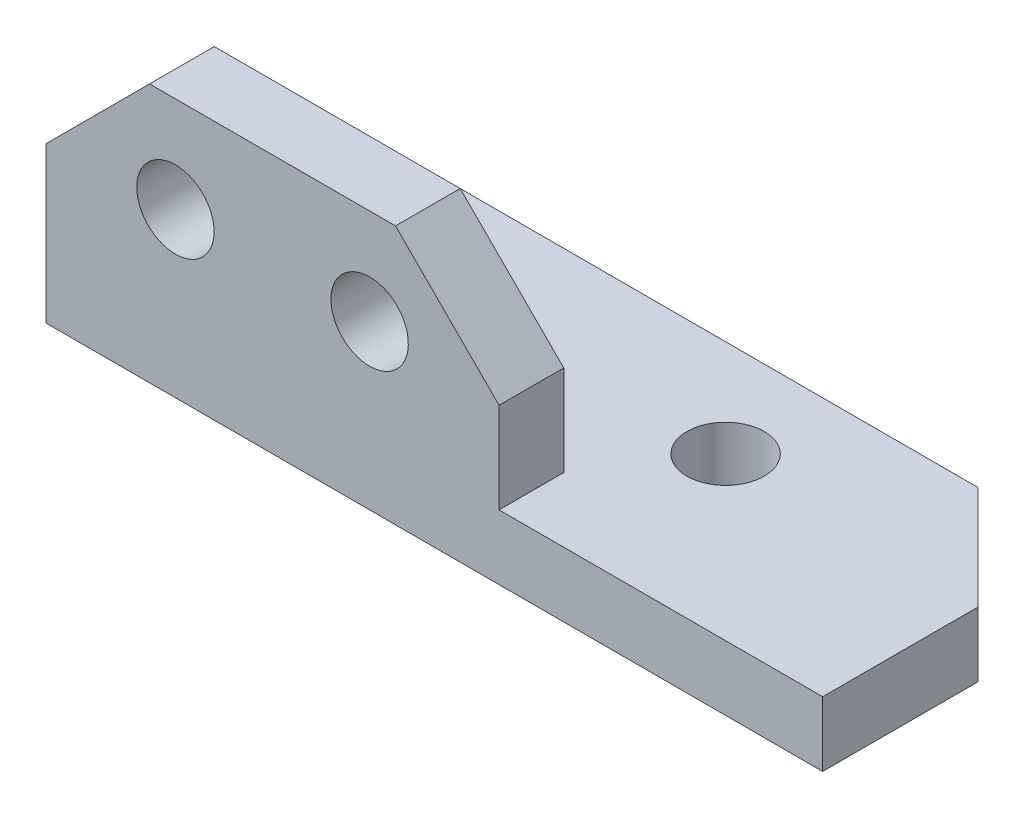
SolidWorks part; units mm, degrees
material "1060 Alloy"
ref_plane "Front Plane" through (0, 0, 0) normal (0, 0, 1) x (1, 0, 0)
ref_plane "Top Plane" through (0, 0, 0) normal (0, 1, 0) x (1, 0, 0)
ref_plane "Right Plane" through (0, 0, 0) normal (1, 0, 0) x (0, 0, -1)
sketch "Sketch1" plane through (0, 0, 0) normal (1, 0, 0) x (0, 0, -1)
  line L0 (-3.175, 9.525) -> (-3.175, -3.175)
  line L1 (-3.175, -3.175) -> (9.525, -3.175)
  line L2 (9.525, -3.175) -> (9.525, 0)
  line L3 (9.525, 0) -> (0, 0)
  line L4 (0, 0) -> (0, 9.525)
  line L5 (0, 9.525) -> (-3.175, 9.525)
  dimension "D1" = 12.7
  dimension "D2" = 12.7
  dimension "D3" = 9.525
  dimension "D5" = 3.175
extrude "Extrude1" add sketch "Sketch1" along normal blind 19.05 and the other way blind 19.05
hole_wizard "#6 Clearance Hole1" positions "3DSketch1" profile "Sketch2" hole size "#6" standard "Ansi Inch"
sketch3d "3DSketch1"
  line L1 (19.05, 0, -9.525) -> (-19.05, 0, -9.525) construction
  line L2 (-19.05, 0, -9.525) -> (-19.05, 0, 0) construction
  line L3 (-19.05, 0, 0) -> (-19.05, 9.525, 0) construction
  line L6 (19.05, 9.525, 0) -> (-19.05, 9.525, 0) construction
  point P0 (6.35, 0, -4.7625)
  point P2 (-6.35, 0, -4.7625)
  point P6 (-12.7, 4.826, 0)
  point P21 (-3.175, 4.826, 0)
  dimension "D1" = 12.7
  dimension "D2" = 4.7625
  dimension "D3" = 12.7
  dimension "D4" = 6.35
  dimension "D5" = 4.699
  dimension "D6" = 9.525
sketch "Sketch2" plane through (6.35, 0, -4.7625) normal (1, 0, 0) x (0, 0, 1)
  line L0 (0, 0) -> (0, 7.4908)
  line L1 (0, 7.4908) -> (1.8986, 6.35)
  line L2 (1.8986, 6.35) -> (1.8986, 0)
  line L5 (1.8986, 0) -> (0, 0)
  line L10 (0, 7.4908) -> (-1.8987, 6.35) construction
  line L11 (0, -6.35) -> (0, 107.95) construction
  dimension "Hole Dia." = 3.7973
  dimension "Hole Depth" = 6.35
  dimension "Drill Angle" = 118
sketch "Sketch3" plane through (0, 0, 0) normal (0, 0, -1) x (-1, 0, 0)
  line L0 (-19.05, 0) -> (19.05, 0) construction
  line L1 (-19.05, 9.525) -> (-3.175, 9.525)
  line L2 (-19.05, 9.525) -> (-19.05, 0)
  line L3 (-19.05, 0) -> (-3.175, 0)
  line L4 (-3.175, 9.525) -> (-3.175, 0)
  dimension "D1" = 15.875
extrude "Cut-Extrude1" cut sketch "Sketch3" against normal through all
chamfer "Chamfer1" distance 5.08 angle 45 4 edges at (19.05, -1.5875, -9.525) (-19.05, -1.5875, -9.525) (-19.05, 9.525, 1.5875) (3.175, 9.525, 1.5875)
